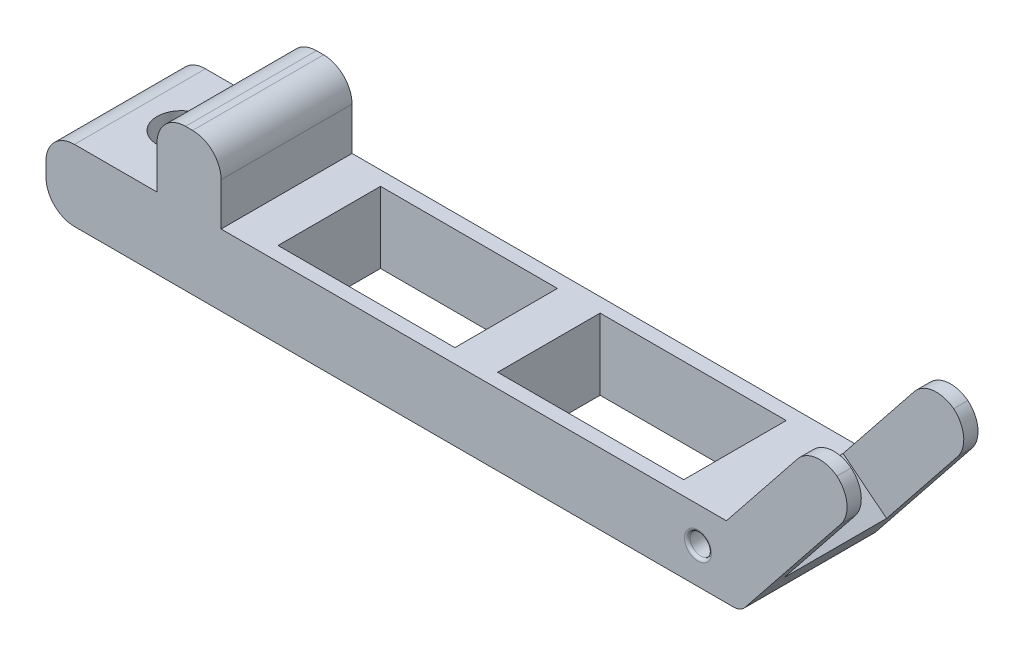
SolidWorks part; units mm, degrees
ref_plane "Front Plane" through (0, 0, 0) normal (0, 0, 1) x (1, 0, 0)
ref_plane "Top Plane" through (0, 0, 0) normal (0, 1, 0) x (1, 0, 0)
ref_plane "Right Plane" through (0, 0, 0) normal (1, 0, 0) x (0, 0, -1)
sketch "Szkic1" plane through (0, 0, 0) normal (0, 0, 1) x (1, 0, 0)
  line L6 (-27646.5587, -28.9023) -> (-27646.5587, -33.9023)
  line L7 (-27646.5587, -33.9023) -> (-27597.7587, -33.9023)
  line L8 (-27597.7587, -33.9023) -> (-27589.4735, -23.5176)
  line L9 (-27589.4735, -23.5176) -> (-27592.5221, -21.0854)
  line L10 (-27592.5221, -21.0854) -> (-27598.7587, -28.9023)
  line L11 (-27598.7587, -28.9023) -> (-27634.2587, -28.9023)
  line L12 (-27638.7587, -28.9023) -> (-27638.7587, -23.9023)
  line L13 (-27638.7587, -23.9023) -> (-27634.2587, -23.9023)
  line L14 (-27634.2587, -23.9023) -> (-27634.2587, -28.9023)
  line L15 (-27638.7587, -28.9023) -> (-27646.5587, -28.9023)
  line L16 (-27600.7587, -28.9023) -> (-27600.7587, -33.9023) construction
  circle A0 centre (-27600.7587, -31.4023) radius 0.75
  point P12 (-27600.7587, -31.4023)
  dimension "D9" = 1.5
  dimension "D1" = 3.9
  dimension "D2" = 47.8
  dimension "D3" = 10
  dimension "D4" = 5
  dimension "D5" = 48.8
  dimension "D6" = 4.5
  dimension "D7" = 5
  dimension "D8" = 7.8
  dimension "D10" = 2
extrude "Dodanie-wyciągnięcie1" add sketch "Szkic1" along normal blind 9.2
fillet "Zaokrąglenie1" radius 2 4 edges at (-27646.5587, -33.9023, 4.6) (-27634.2587, -23.9023, 4.6) (-27638.7587, -23.9023, 4.6) (-27646.5587, -28.9023, 4.6)
fillet "Zaokrąglenie3" radius 1 1 edges at (-27597.7587, -33.9023, 4.6)
ref_plane "Płaszczyzna1" through (0, -28.9023, 0) normal (0, 1, 0) x (1, 0, 0)
sketch "Szkic2" plane through (0, -28.9023, 0) normal (0, 1, 0) x (1, 0, 0)
  line L0 (-27641.6587, 0) -> (-27641.6587, -9.2) construction
  line L1 (-27638.7587, 0) -> (-27644.5587, 0) construction
  line L2 (-27638.7587, -9.2) -> (-27644.5587, -9.2) construction
  circle A0 centre (-27641.6587, -4.6) radius 1.7
  point P6 (-27641.6587, -4.6)
  dimension "D1" = 3.4
extrude "Wytnij-wyciągnięcie1" cut sketch "Szkic2" against normal through all
ref_plane "Płaszczyzna2" through (0, -28.9023, 0) normal (0, 1, 0) x (1, 0, 0)
sketch "Szkic3" plane through (0, -28.9023, 0) normal (0, 1, 0) x (1, 0, 0)
  line L0 (-27634.2587, -4.6) -> (-27598.7587, -4.6) construction
  line L1 (-27634.2587, -9.2) -> (-27634.2587, 0) construction
  line L2 (-27598.7587, -9.2) -> (-27598.7587, 0) construction
  line L3 (-27598.7587, -9.2) -> (-27634.2587, -9.2) construction
  line L4 (-27602.7587, -8.2) -> (-27615.8325, -8.2)
  line L5 (-27602.7587, -8.2) -> (-27602.7587, -1)
  line L6 (-27602.7587, -1) -> (-27615.8325, -1)
  line L7 (-27615.8325, -8.2) -> (-27615.8325, -1)
  line L8 (-27602.7587, -8.2) -> (-27615.8325, -1) construction
  line L9 (-27602.7587, -1) -> (-27615.8325, -8.2) construction
  line L10 (-27631.2587, -1) -> (-27618.8325, -1)
  line L11 (-27631.2587, -1) -> (-27631.2587, -8.2)
  line L12 (-27631.2587, -8.2) -> (-27618.8325, -8.2)
  line L13 (-27618.8325, -1) -> (-27618.8325, -8.2)
  line L14 (-27631.2587, -1) -> (-27618.8325, -8.2) construction
  line L15 (-27631.2587, -8.2) -> (-27618.8325, -1) construction
  point P6 (-27609.2956, -4.6)
  point P11 (-27625.0456, -4.6)
  dimension "D1" = 3
  dimension "D2" = 4
  dimension "D3" = 3
  dimension "D4" = 1
extrude "Wytnij-wyciągnięcie2" cut sketch "Szkic3" against normal through all
ref_plane "Płaszczyzna3" through (-16850.0467, 13443.5022, 0) normal (-0.7817, 0.6237, 0) x (0, 0, 1)
sketch "Szkic4" plane through (-16850.0467, 13443.5022, 0) normal (-0.7817, 0.6237, 0) x (0, 0, 1)
  line L0 (9.2, -17234.8628) -> (0, -17234.8628) construction
  line L1 (1, -17234.8628) -> (8.2, -17234.8628)
  line L2 (1, -17234.8628) -> (1, -17222.0924)
  line L3 (1, -17222.0924) -> (8.2, -17222.0924)
  line L4 (8.2, -17234.8628) -> (8.2, -17222.0924)
  line L5 (0, -17224.8628) -> (0, -17234.8628) construction
  dimension "D1" = 7.2
  dimension "D2" = 1
extrude "Wytnij-wyciągnięcie3" cut sketch "Szkic4" against normal through all
ref_plane "Płaszczyzna4" through (0, 0, 1) normal (0, 0, 1) x (1, 0, 0)
sketch "Szkic5" plane through (0, 0, 1) normal (0, 0, 1) x (1, 0, 0)
  line L0 (-27590.9978, -22.3015) -> (-27597.2344, -30.1185) construction
  line L1 (-27592.5221, -21.0854) -> (-27589.4735, -23.5176) construction
  line L2 (-27595.7101, -31.3346) -> (-27598.7587, -28.9023) construction
  circle A0 centre (-27592.3166, -23.9544) radius 0.5
  dimension "D1" = 1
extrude "Dodanie-wyciągnięcie2" [suppressed] add sketch "Szkic5" along normal up to next
fillet "Zaokrąglenie4" radius 2 4 edges at (-27589.4735, -23.5176, 0.5) (-27592.5221, -21.0854, 0.5) (-27589.4735, -23.5176, 8.7) (-27592.5221, -21.0854, 8.7)
fillet "Zaokrąglenie5" radius 1 1 edges at (-27643.3587, -33.9023, 4.6)
ref_axis "Oś1" through (-27641.6587, -32.9023, 4.6) along (0, 1, 0)
ref_point "Punkt1"
ref_point "Punkt2"
fillet "Zaokrąglenie7" radius 0.2 2 edges at (-27600.0087, -31.4023, 9.2) (-27600.0087, -31.4023, 0)
ref_plane "Płaszczyzna Dolnia" through (0, -33.9023, 0) normal (0, -1, 0) x (-1, 0, 0)
